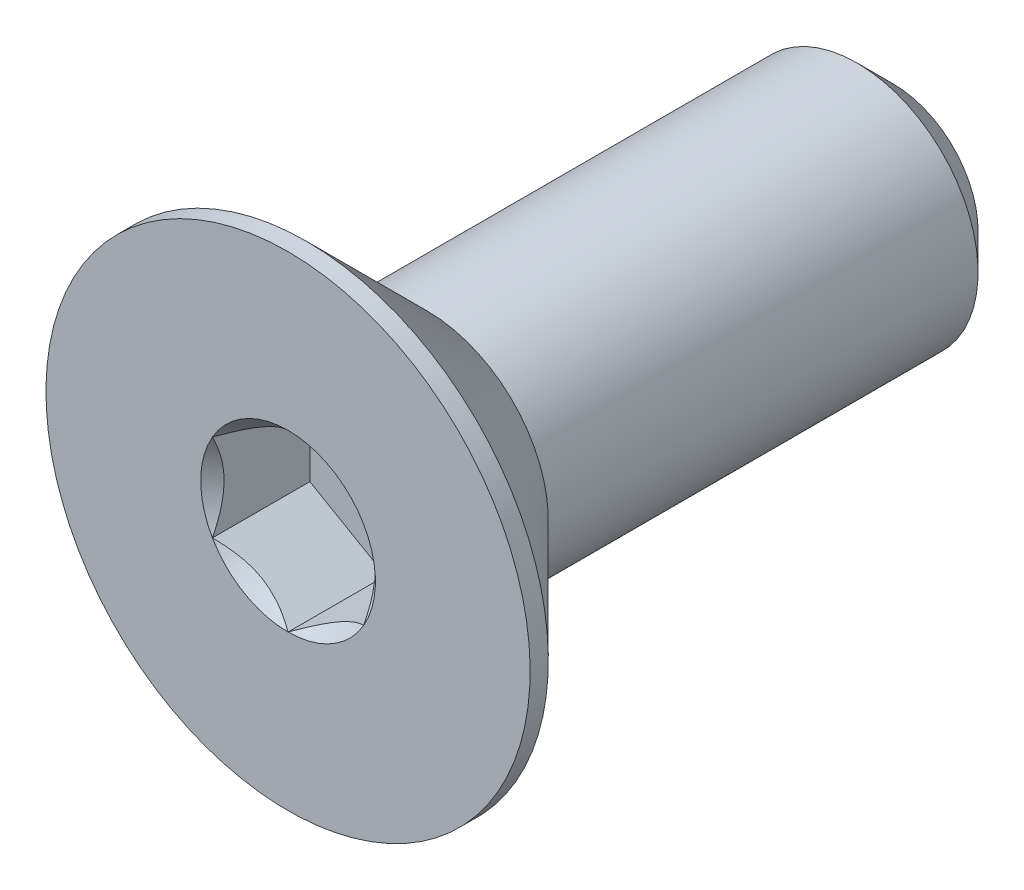
SolidWorks part; units mm, degrees
material "Alloy Steel"
ref_plane "Front" through (0, 0, 0) normal (0, 0, 1) x (1, 0, 0)
ref_plane "Top" through (0, 0, 0) normal (0, 1, 0) x (1, 0, 0)
ref_plane "Right" through (0, 0, 0) normal (1, 0, 0) x (0, 0, -1)
sketch "Sketch1" plane through (0, 0, 0) normal (1, 0, 0) x (0, 0, -1)
  line L0 (-5, 4) -> (-4.7, 4) construction
  line L1 (-4.7, 4) -> (-2.7, 2) construction
  line L2 (-5, 2) -> (5, 2) construction
  line L3 (5, 2) -> (5, 0) construction
  line L4 (5, 0) -> (-5, 0) construction
  line L5 (-5, 0) -> (-5, 4) construction
  line L6 (-5, 4) -> (-5, -4) construction
  line L7 (5, 2) -> (5, -2) construction
  line L8 (-5, -4) -> (-4.7, -4) construction
  line L9 (-4.7, -4) -> (-2.7, -2) construction
  line L11 (-5, 2) -> (-5, 0) construction
  line L12 (-2.7, 2) -> (-2.7, 0) construction
  line L13 (4.9563, 2.0758) -> (5.3063, 1.4696) construction
  line L14 (5.3063, 1.4696) -> (5.6562, 2.0758) construction
  line L15 (5.6562, 2.0758) -> (4.9563, 2.0758) construction
  line L16 (5.3063, 2.0758) -> (5.3063, 2) construction
  line L17 (5.3063, 2) -> (5.3063, 1.5453) construction
  line L18 (5.3063, 1.5453) -> (5.3063, 1.4696) construction
  line L19 (5.3063, 2.0379) -> (5.6344, 2.0379) construction
  line L20 (5.3063, 2.0379) -> (4.9781, 2.0379) construction
  line L21 (5, 2) -> (5.6125, 2) construction
  line L22 (5.2625, 1.5453) -> (5.35, 1.5453) construction
  line L23 (5, -2) -> (-2.7, -2) construction
  point P10 (3.25, -2)
  point P24 (-2.7, 2)
  point P30 (0, 0)
  dimension "Head Diameter" = 8
  dimension "Head Height" = 2.3
  dimension "Length" = 10
  dimension "Countersink Angle" = 90
  dimension "Thread Pitch" = 0.7
  dimension "D2" = 0.0875
  dimension "Minimum Thread Length" = 7.7
  dimension "Thread Size" = 4
  dimension "D1" = 1.75
sketch "Sketch2" plane through (0, 0, 0) normal (0, 0, 1) x (1, 0, 0)
  line L1 (0, 1.4434) -> (-1.25, 0.7217) construction
  line L2 (-1.25, 0.7217) -> (-1.25, -0.7217) construction
  line L3 (-1.25, -0.7217) -> (0, -1.4434) construction
  line L4 (0, -1.4434) -> (1.25, -0.7217) construction
  line L5 (1.25, -0.7217) -> (1.25, 0.7217) construction
  line L6 (1.25, 0.7217) -> (0, 1.4434) construction
  circle A0 centre (0, 0) radius 1.25 construction
  dimension "Drive Size" = 2.5
sketch "Sketch3" plane through (0, 0, 0) normal (1, 0, 0) x (0, 0, -1)
  line L0 (-5, 2) -> (5, 2)
  line L1 (5, 2) -> (5, 0)
  line L2 (5, 0) -> (-5, 0)
  line L3 (-5, 0) -> (-5, 2)
revolve "Revolve1" add sketch "Sketch3" angle 360 about L4
chamfer "Chamfer1" distance 0.6 angle 45 1 edges at (0, 2, -5)
sketch "Sketch6" plane through (0, 0, 0) normal (1, 0, 0) x (0, 0, -1)
  line L0 (-5, 4) -> (-4.7, 4)
  line L1 (-4.7, 4) -> (-2.7, 2)
  line L2 (-2.7, 2) -> (-2.7, 0)
  line L3 (-2.7, 0) -> (-5, 0)
  line L4 (-5, 0) -> (-5, 4)
revolve "Revolve2" add sketch "Sketch6" angle 360 about L4
sketch "Sketch8" plane through (0, 0, 5) normal (0, 0, 1) x (1, 0, 0)
  line L0 (0, 1.4434) -> (-1.25, 0.7217) construction
  line L1 (1.25, 0.7217) -> (0, 1.4434) construction
  line L2 (1.25, -0.7217) -> (1.25, 0.7217) construction
  line L3 (0, -1.4434) -> (1.25, -0.7217) construction
  line L4 (-1.25, 0.7217) -> (-1.25, -0.7217) construction
  line L5 (-1.25, -0.7217) -> (0, -1.4434) construction
  line L6 (0, 1.4434) -> (-1.25, 0.7217)
  line L7 (1.25, 0.7217) -> (0, 1.4434)
  line L8 (1.25, -0.7217) -> (1.25, 0.7217)
  line L9 (0, -1.4434) -> (1.25, -0.7217)
  line L10 (-1.25, 0.7217) -> (-1.25, -0.7217)
  line L11 (-1.25, -0.7217) -> (0, -1.4434)
extrude "Cut-Extrude1" cut sketch "Sketch8" against normal blind 1.61
sketch "Sketch9" plane through (0, 0, 5) normal (0, 0, 1) x (1, 0, 0)
  circle A0 centre (0, 0) radius 1.4434
extrude "Cut-Extrude2" cut sketch "Sketch9" against normal up to next (1.61 mm away) draft 45
ref_plane "Plane1" [suppressed] through (0, 0, 2.7) normal (0, 0, 1) x (1, 0, 0)
split "Split1" [suppressed] bodies to split 124
sketch "Sketch4" [suppressed] plane through (0, 0, -5) normal (0, 0, -1) x (-1, 0, 0)
  circle A0 centre (0, 0) radius 2 construction
  circle A1 centre (0, 0) radius 2
curve "Helix/Spiral1" [suppressed] pitch 0.7 height 8.4 turns 12
sketch "Sketch10" [suppressed] plane through (0, 0, 0) normal (1, 0, 0) x (0, 0, -1)
  line L0 (4.9781, 2.0379) -> (5.6344, 2.0379)
  line L1 (5.6344, 2.0379) -> (5.35, 1.5453)
  line L2 (5.35, 1.5453) -> (5.2625, 1.5453)
  line L3 (5.2625, 1.5453) -> (4.9781, 2.0379)
sweep "Cut-Sweep1" [suppressed] cut profiles "Sketch10" path "Helix/Spiral1"
equation "\"D2@Sketch1\" = \"Thread Pitch@Sketch1\" / 8"
equation "\"D4@Helix/Spiral1\"=\"Thread Pitch@Sketch1\""
equation "\"D3@Helix/Spiral1\"=\"Minimum Thread Length@Sketch1\"+\"Thread Pitch@Sketch1\""
equation "\"D1@Chamfer1\"=\"Thread Size@Sketch1\"*.15"
equation "\"D1@Cut-Extrude1\"=\"Head Height@Sketch1\"*.7"
equation "\"D1@Sketch1\"=\"Thread Pitch@Sketch1\"*2.5"
